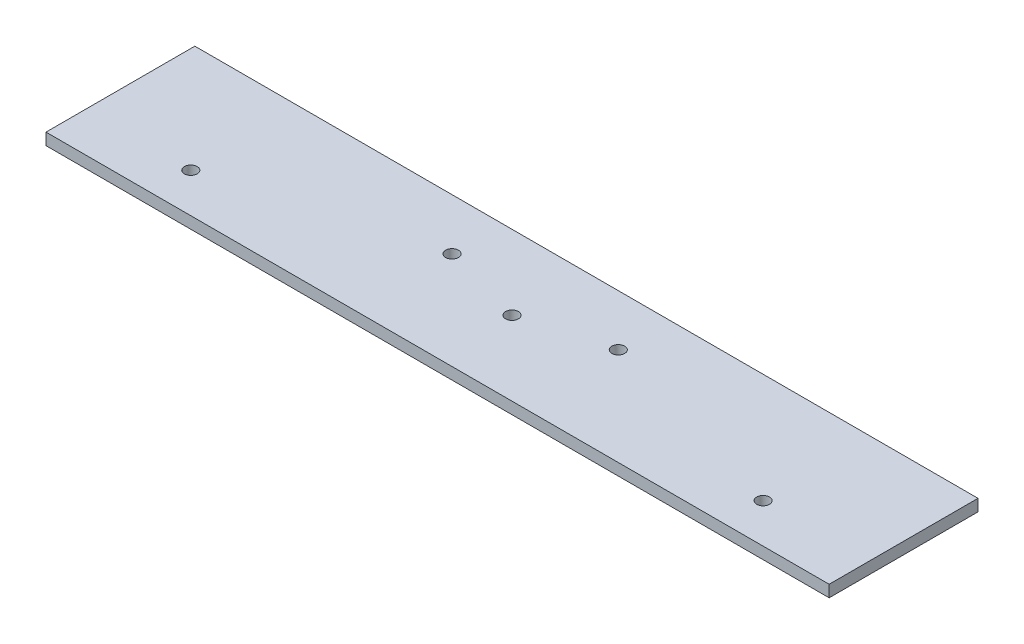
SolidWorks part; units mm, degrees
ref_plane "Front Plane" through (0, 0, 0) normal (0, 0, 1) x (1, 0, 0)
ref_plane "Top Plane" through (0, 0, 0) normal (0, 1, 0) x (1, 0, 0)
ref_plane "Right Plane" through (0, 0, 0) normal (1, 0, 0) x (0, 0, -1)
sketch "Sketch1" plane through (0, 0, 0) normal (0, 1, 0) x (1, 0, 0)
  line L0 (-71, -8.695) -> (71, -8.695) construction
  line L1 (0, 0) -> (0, 5.75) construction
  line L2 (-97.1504, -18.4656) -> (97.1504, -18.4656)
  line L3 (-97.1504, -18.4656) -> (-97.1504, 18.4656)
  line L4 (-97.1504, 18.4656) -> (97.1504, 18.4656)
  line L5 (97.1504, -18.4656) -> (97.1504, 18.4656)
  line L6 (-97.1504, -18.4656) -> (97.1504, 18.4656) construction
  line L7 (-97.1504, 18.4656) -> (97.1504, -18.4656) construction
  line L8 (0, 5.75) -> (-20.62, 5.75) construction
  line L9 (0, 0) -> (0, 14.6731) construction
  circle A0 centre (-71, -8.695) radius 1.5875
  circle A1 centre (71, -8.695) radius 1.5875
  circle A2 centre (0, 0) radius 1.5875
  circle A3 centre (-20.62, 5.75) radius 1.5875
  circle A4 centre (20.62, 5.75) radius 1.5875
  point P6 (0, 0)
  dimension "D2" = 3.175
  dimension "D1" = 142
  dimension "D3" = 5.75
  dimension "D4" = 20.62
  dimension "D5" = 8.695
extrude "Boss-Extrude1" add sketch "Sketch1" along normal mid plane 2.921
sketch "Sketch2" plane through (0, -1.4605, 0) normal (0, -1, 0) x (-1, 0, 0)
  line L0 (20.62, 5.75) -> (13.8061, 5.75) construction
